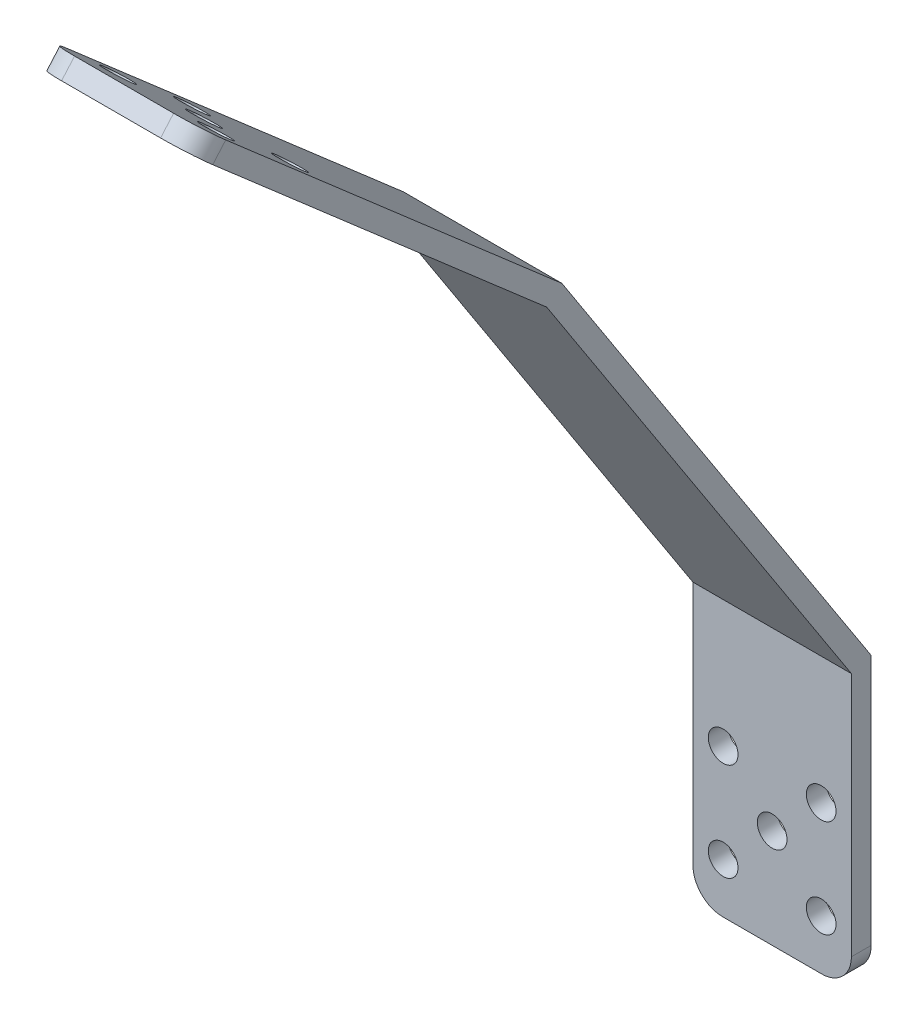
SolidWorks part; units mm, degrees
ref_plane "前视" through (0, 0, 0) normal (0, 0, 1) x (1, 0, 0)
ref_plane "上视" through (0, 0, 0) normal (0, 1, 0) x (1, 0, 0)
ref_plane "右视" through (0, 0, 0) normal (1, 0, 0) x (0, 0, -1)
sketch "草图1" plane through (0, 0, 0) normal (0, 0, 1) x (1, 0, 0)
  line L0 (0, 14.7362) -> (0, -14.2678) construction
  line L1 (-15.916, 0) -> (15.5486, 0) construction
  line L3 (-8, 24) -> (8, 24)
  line L4 (-8, 24) -> (-8, -24)
  line L5 (-8, -24) -> (8, -24)
  line L6 (8, 24) -> (8, -24)
  line L7 (-8, 24) -> (8, -24) construction
  line L8 (-8, -24) -> (8, 24) construction
  point P5 (0, 0)
  dimension "D1" = 16
  dimension "D2" = 48
extrude "凸台-拉伸1" add sketch "草图1" along normal blind 3
sketch "草图2" plane through (0, 0, 3) normal (0, 0, 1) x (1, 0, 0)
  line L0 (-7.7762, 0) -> (8.6691, 0) construction
  line L1 (0, 11.5397) -> (0, -11.8699) construction
  line L2 (-7.9817, -14) -> (8.6691, -14) construction
  line L3 (-8, -24) -> (8, -24) construction
  circle A0 centre (0, -14) radius 7 construction
  circle A1 centre (-4.9497, -9.0503) radius 1.5
  circle A2 centre (0, -14) radius 1.5
  circle A3 centre (4.9497, -9.0503) radius 1.5
  circle A4 centre (4.9497, -18.9497) radius 1.5
  circle A5 centre (-4.9497, -18.9497) radius 1.5
  point P21 (0, -14)
  dimension "D2" = 3
  dimension "D3" = 14
  dimension "D4" = 3
  dimension "D1" = 10
  dimension "D5" = 4
extrude "切除-拉伸1" cut sketch "草图2" against normal through all
ref_plane "基准面1" through (0, 12.1847, -10.592) normal (0, 0.7547, -0.6561) x (-1, 0, 0)
sketch "草图3" plane through (0, 12.1847, -10.592) normal (0, 0.7547, -0.6561) x (-1, 0, 0)
  line L0 (-8, 18.0095) -> (8, 18.0095) construction
  line L1 (-8, 18.0095) -> (8, 18.0095)
  line L2 (0, 34.8976) -> (0, -9.373) construction
  line L3 (-18.8539, 0) -> (18.6715, 0) construction
  line L4 (-8, 18.0095) -> (-8, 106.0095)
  line L5 (-8, 106.0095) -> (8, 106.0095)
  line L6 (8, 106.0095) -> (8, 18.0095)
  dimension "D1" = 88
extrude "凸台-拉伸2" add sketch "草图3" along normal blind 3 separate body
sketch "草图4" plane through (0, 11.8153, 13.592) normal (0, -0.6561, -0.7547) x (-1, 0, 0)
  line L0 (-8, 19.1449) -> (8, 19.1449) construction
  line L1 (-8, 19.1449) -> (-8, 16.1449) construction
  line L2 (-8, 16.1449) -> (8, 16.1449) construction
  line L3 (8, 19.1449) -> (8, 16.1449) construction
  line L4 (-8, 19.1449) -> (8, 19.1449)
  line L5 (-8, 19.1449) -> (-8, 16.1449)
  line L6 (-8, 16.1449) -> (8, 16.1449)
  line L7 (8, 19.1449) -> (8, 16.1449)
extrude "凸台-拉伸3" add sketch "草图4" along normal blind 2
sketch "草图5" plane through (0, 12.1847, -10.592) normal (0, -0.7547, 0.6561) x (1, 0, 0)
  line L0 (0, 80.4499) -> (0, -20.8419) construction
  line L1 (-25.5488, 95.34) -> (29.0902, 95.34) construction
  circle A0 centre (0, 95.34) radius 1.5
  circle A1 centre (0, 95.34) radius 7 construction
  circle A2 centre (-4.9497, 100.2897) radius 1.5
  circle A3 centre (4.9497, 100.2897) radius 1.5
  circle A4 centre (4.9497, 90.3903) radius 1.5
  circle A5 centre (-4.9497, 90.3903) radius 1.5
  point P19 (0, 95.34)
  dimension "D2" = 3
  dimension "D3" = 14
  dimension "D4" = 3
  dimension "D1" = 95.34
  dimension "D5" = 4
extrude "切除-拉伸2" cut sketch "草图5" against normal through all
fillet "圆角3" radius 3 4 edges at (-8, -24, 1.5) (8, -24, 1.5) (8, 82.8653, 68.4304) (-8, 82.8653, 68.4304)
sketch "草图6" plane through (-8, 0, 0) normal (-1, 0, 0) x (0, 0, 1)
  line L0 (33.5315, 50.5406) -> (3, 3.4725)
  line L1 (3, 24) -> (3, -21) construction
  line L3 (31.2445, 52.5276) -> (0, 4.3603)
  line L4 (-0.4776, 24.952) -> (65.1821, 82.0291) construction
  line L5 (0, 24) -> (0, -21) construction
  line L6 (3, 24) -> (67.1503, 79.765) construction
  line L7 (31.2445, 52.5276) -> (33.5315, 50.5406)
  line L8 (0, 4.3603) -> (3, 3.4725)
  dimension "D1" = 3
extrude "凸台-拉伸4" add sketch "草图6" against normal up to surface (16 mm away) up to face at (8, 27.0933, 17.2756)
ref_plane "基准面2" through (-8, 24.952, -0.4776) normal (0, 0.6561, 0.7547) x (1, 0, 0)
sketch "草图9" plane through (8, 0, 0) normal (1, 0, 0) x (0, 0, -1)
  line L0 (0, 4.3603) -> (-31.2445, 52.5276)
  line L1 (0.4776, 24.952) -> (-65.1821, 82.0291) construction
  line L2 (-3, 8.9852) -> (-25.3322, 43.4131) construction
  line L3 (0, -21) -> (0, 24) construction
  line L4 (0, 4.3603) -> (6.0528, 30.6803)
  line L5 (6.0528, 30.6803) -> (-31.2445, 52.5276)
extrude "切除-拉伸3" cut sketch "草图9" against normal through all
sketch "草图11" plane through (-8, 0, 0) normal (-1, 0, 0) x (0, 0, 1)
  line L0 (0, 4.3603) -> (3, 3.4725)
  line L1 (31.2445, 52.5276) -> (33.5315, 50.5406)
  line L2 (76.3463, 89.084) -> (32.7692, 51.203)
  line L3 (32.7692, 51.203) -> (2, 3.7684)
  line L4 (2, 3.7684) -> (2, -26.5916)
  line L5 (2, -26.5916) -> (76.3463, 89.084)
  line L6 (0, 4.3603) -> (0, -21) construction
  line L8 (3, 3.4725) -> (33.5315, 50.5406) construction
  line L10 (33.5315, 50.5406) -> (67.1503, 79.765) construction
  point P13 (76.3463, 89.084)
  point P15 (71.3832, 83.6431)
  line M8 (0, -21) -> (3, -21)
  line M9 (3, -21) -> (3, 3.4725)
  line M10 (3, 3.4725) -> (33.5315, 50.5406)
  line M11 (33.5315, 50.5406) -> (67.1503, 79.765)
  line M12 (67.1503, 79.765) -> (65.1821, 82.0291)
  dimension "D1" = 2
extrude "切除-拉伸4" cut sketch "草图11" against normal through all contours L4 L5 L2 M12 M11 M10 M9 M8 | L2 L1 M12 M11 | L1 L3 L0 M10 | L0 L4 M8 M9 region at (-8, 27.2464, 17.8246) region at (-8, -8.6896, 2.499) region at (-8, 29.1159, 30.0083) region at (-8, 65.5073, 49.9861)
